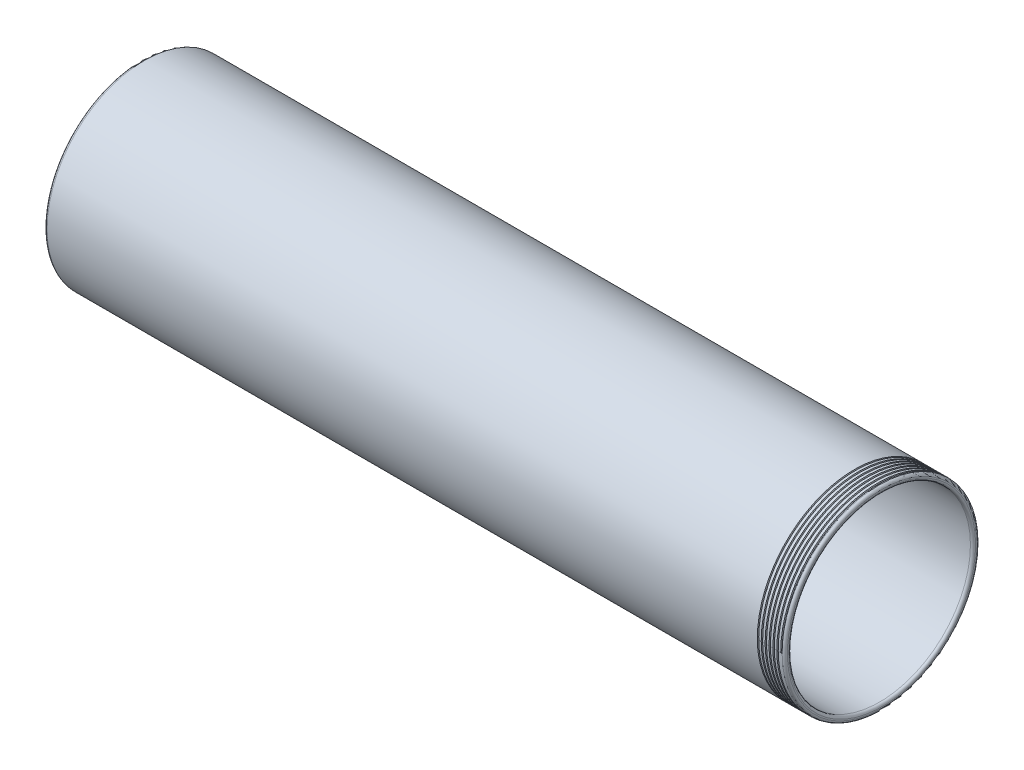
SolidWorks part; units mm, degrees
material "1060-H12"
ref_plane "Płaszczyzna przednia" through (0, 0, 0) normal (0, 0, 1) x (1, 0, 0)
ref_plane "Płaszczyzna górna" through (0, 0, 0) normal (0, 1, 0) x (1, 0, 0)
ref_plane "Płaszczyzna prawa" through (0, 0, 0) normal (1, 0, 0) x (0, 0, -1)
sketch "Szkic1" plane through (0, 0, 0) normal (0, 0, 1) x (1, 0, 0)
  line L0 (0, 0) -> (105558.8307, 0) construction
  line L1 (-158.6842, 75) -> (411.3158, 75)
  line L2 (-158.6842, 75) -> (-158.6842, 0)
  line L3 (411.3158, 75) -> (411.3158, 0)
  line L4 (-158.6842, 70) -> (411.3158, 70)
  dimension "D1" = 150
  dimension "D2" = 140
  dimension "D3" = 570
revolve "Obrót1" add sketch "Szkic1" angle 360 about L0 region at (126.3158, 72.5, 0)
fillet "Zaokrąglenie1" radius 2 4 edges at (411.3158, 0, 70) (411.3158, 0, 75) (-158.6842, 0, 70) (-158.6842, 0, 75)
cosmetic thread "Oznaczenie gwintu1" parameters "D1"=20, "D2"=140
ref_plane "Płaszczyzna2" through (409.3158, 0, 0) normal (1, 0, 0) x (0, 0, -1)
thread "Gwint1" pitch 1.25 method cut profile "Thread Profile1" start angle 0, offset 0, length 20, pitch 3, diameter 150
ref_plane "Płaszczyzna1" through (409.3158, 0, 75) normal (0, -1, 0) x (0, 0, 1)
sketch "Thread Profile1" plane through (409.3158, 0, 75) normal (0, -1, 0) x (0, 0, 1)
  line L0 (0, 0) -> (0, 1.25) construction
  line L11 (0, 0) -> (0, 1.0937)
  line L12 (0, 1.0937) -> (-0.6766, 0.7031)
  line L13 (-0.6766, 0.7031) -> (-0.6766, 0.3906)
  line L15 (-0.6766, 0.3906) -> (0, 0)
  line L17 (-0.6766, 0.5469) -> (0, 0.5469) construction
  point P2 (0, 0)
  dimension "Pitch" = 1.25
  dimension "Profile_Angle" = 60
  dimension "Profile_Land" = 0.3125
  dimension "Profile_Height" = 0.6766
